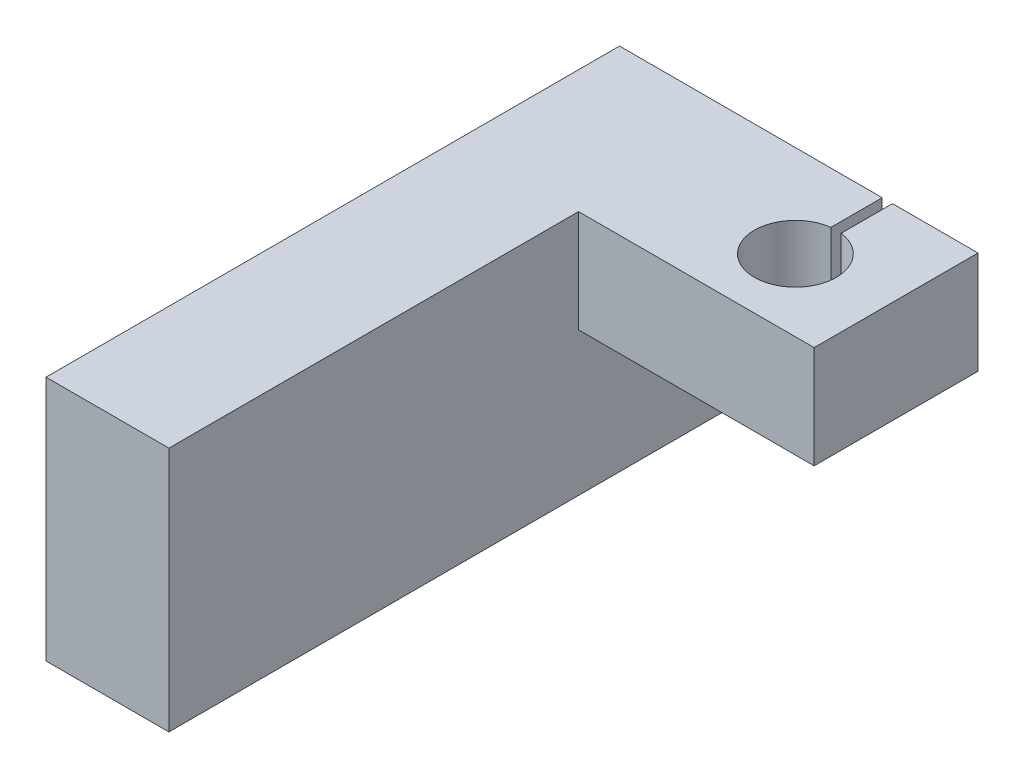
SolidWorks part; units mm, degrees
ref_plane "Front Plane" through (0, 0, 0) normal (0, 0, 1) x (1, 0, 0)
ref_plane "Top Plane" through (0, 0, 0) normal (0, 1, 0) x (1, 0, 0)
ref_plane "Right Plane" through (0, 0, 0) normal (1, 0, 0) x (0, 0, -1)
sketch "Sketch2" plane through (0, 0, 0) normal (0, 1, 0) x (1, 0, 0)
  line L1 (0, 0) -> (12, 0)
  line L2 (0, 0) -> (0, -56)
  line L3 (0, -56) -> (12, -56)
  line L4 (12, 0) -> (12, -56)
  point P4 (12.15, 0)
  point P5 (0, 0)
  point P7 (33.278, 0)
  point P9 (26.16, -51.8975)
  point P11 (23.6902, -55.9547)
  dimension "D1" = 56
  dimension "D2" = 12
extrude "Boss-Extrude1" add sketch "Sketch2" along normal blind 14 contours L2 L3 L4 L1
sketch "Sketch3" plane through (0, 14, 0) normal (0, 1, 0) x (1, 0, 0)
  line L0 (26.15, -5.0114) -> (26.15, -8.98) construction
  line L1 (0, 0) -> (35, 0)
  line L2 (0, 0) -> (0, -56)
  line L3 (0, -56) -> (35, -56)
  line L4 (35, 0) -> (35, -56)
  line L5 (25.65, 0) -> (26.65, 0)
  line L6 (25.65, 0) -> (25.65, -5.0114)
  line L7 (25.65, -5.0114) -> (26.65, -5.0114)
  line L8 (26.65, 0) -> (26.65, -5.0114)
  line L9 (35, -16) -> (12, -16)
  line L10 (12, 0) -> (12, -56) construction
  circle A0 centre (26.15, -8.98) radius 4
  line M2 (12, 0) -> (0, 0)
  line M3 (0, 0) -> (0, -56)
  line M4 (0, -56) -> (12, -56)
  line M5 (12, -56) -> (12, 0)
  dimension "D2" = 8
  dimension "D3" = 8.98
  dimension "D4" = 8.85
  dimension "D1" = 35
  dimension "D5" = 1
  dimension "D6" = 16
extrude "Boss-Extrude2" add sketch "Sketch3" along normal blind 10 contours A0 L6 L1 L3 L4 L8 M5 | M5 M2 M3 M4 region at (6, 14, 28) region at (18.825, 14, 0.2802)
